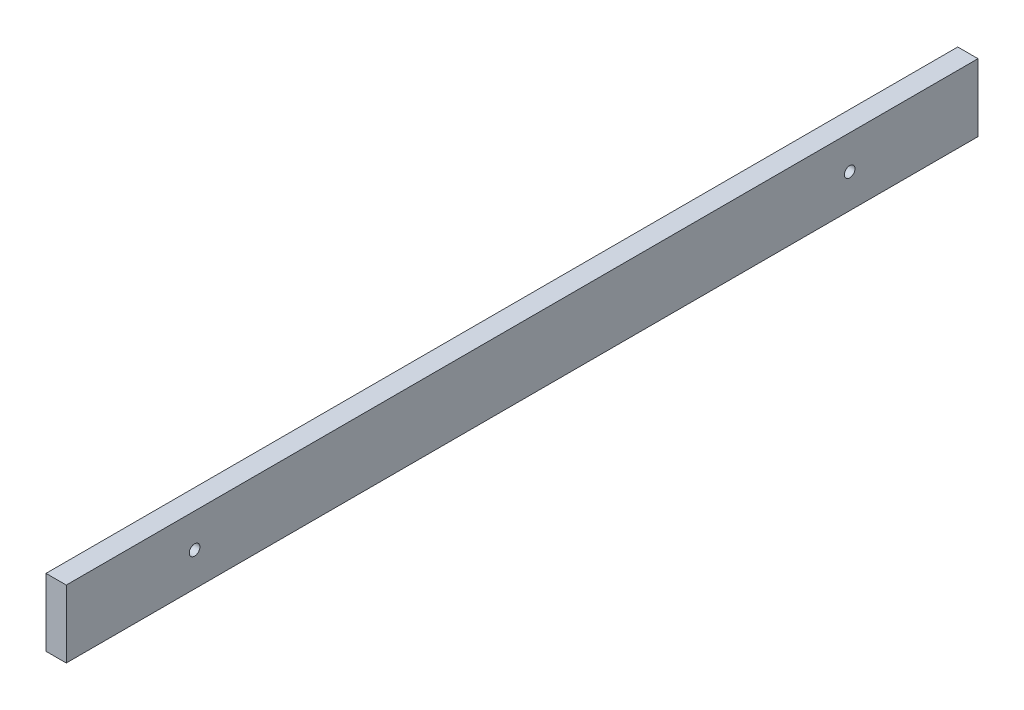
SolidWorks part; units mm, degrees
ref_plane "Alzado" through (0, 0, 0) normal (0, 0, 1) x (1, 0, 0)
ref_plane "Planta" through (0, 0, 0) normal (0, 1, 0) x (1, 0, 0)
ref_plane "Vista lateral" through (0, 0, 0) normal (1, 0, 0) x (0, 0, -1)
sketch "Croquis1" plane through (0, 0, 0) normal (1, 0, 0) x (0, 0, -1)
  line L1 (-135, -10) -> (135, -10)
  line L2 (-135, -10) -> (-135, 10)
  line L3 (-135, 10) -> (135, 10)
  line L4 (135, -10) -> (135, 10)
  line L5 (-135, -10) -> (135, 10) construction
  line L6 (-135, 10) -> (135, -10) construction
  circle A0 centre (97, 0) radius 1.58
  circle A1 centre (-97, 0) radius 1.58
  point P0 (0, 0)
  dimension "D3" = 3.16
  dimension "D5" = 3.16
  dimension "D1" = 270
  dimension "D2" = 20
  dimension "D4" = 38
  dimension "D6" = 38
extrude "Saliente-Extruir1" add sketch "Croquis1" along normal blind 6
